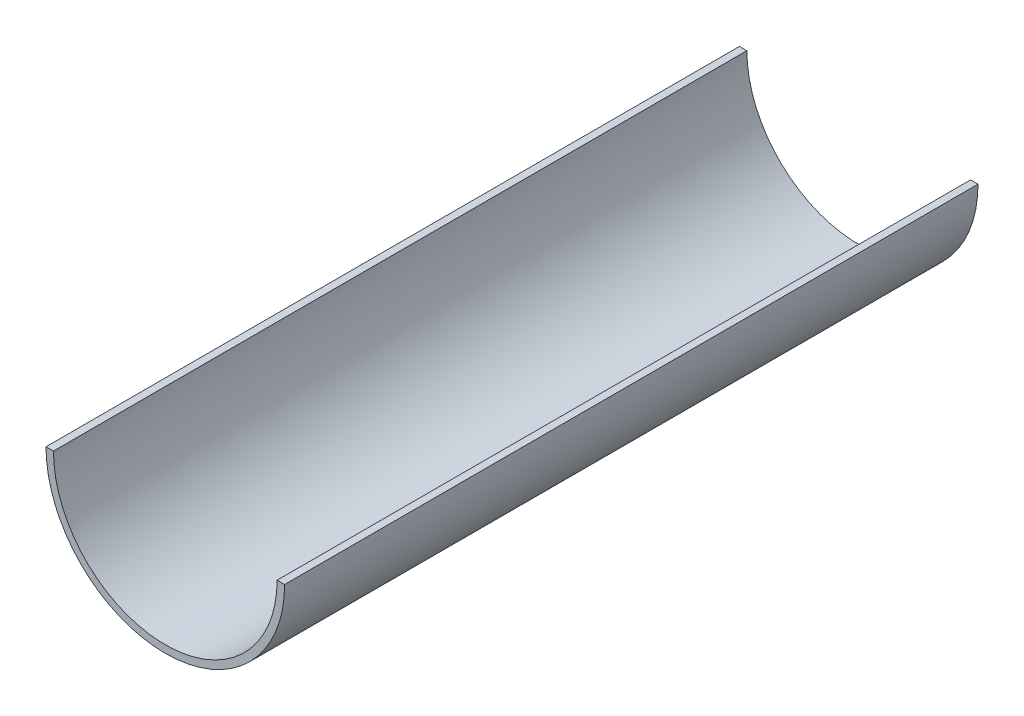
SolidWorks part; units mm, degrees
ref_plane "Alzado" through (0, 0, 0) normal (0, 0, 1) x (1, 0, 0)
ref_plane "Planta" through (0, 0, 0) normal (0, 1, 0) x (1, 0, 0)
ref_plane "Vista lateral" through (0, 0, 0) normal (1, 0, 0) x (0, 0, -1)
sketch "Croquis1" plane through (0, 0, 0) normal (0, 0, 1) x (1, 0, 0)
  line L0 (-16, 0) -> (-15, 0)
  line L1 (15, 0) -> (16, 0)
  arc A0 (-15, 0) -> (15, 0) centre (0, 0) ccw
  arc A1 (-16, 0) -> (16, 0) centre (0, 0) ccw
  dimension "D1" = 32
  dimension "D2" = 30
extrude "Saliente-Extruir1" add sketch "Croquis1" along normal blind 93
